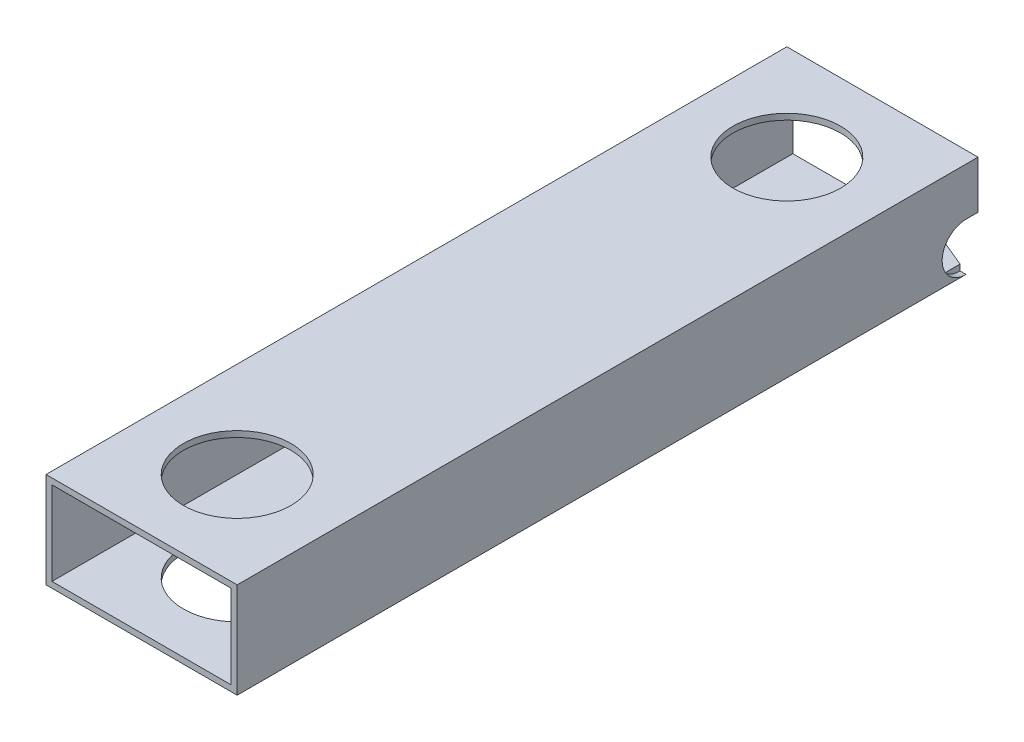
SolidWorks part; units mm, degrees
material "6061 Alloy"
ref_plane "Front Plane" through (0, 0, 0) normal (0, 0, 1) x (1, 0, 0)
ref_plane "Top Plane" through (0, 0, 0) normal (0, 1, 0) x (1, 0, 0)
ref_plane "Right Plane" through (0, 0, 0) normal (1, 0, 0) x (0, 0, -1)
sketch "Sketch1" plane through (0, 0, 0) normal (0, 0, 1) x (1, 0, 0)
  line L0 (-23.8125, 11.1125) -> (23.8125, 11.1125)
  line L2 (-25.4, 12.7) -> (25.4, 12.7)
  line L3 (-25.4, 12.7) -> (-25.4, -12.7)
  line L4 (-25.4, -12.7) -> (25.4, -12.7)
  line L5 (25.4, 12.7) -> (25.4, -12.7)
  line L10 (23.8125, 11.1125) -> (23.8125, -11.1125)
  line L11 (-23.8125, -11.1125) -> (23.8125, -11.1125)
  line L12 (-23.8125, 11.1125) -> (-23.8125, -11.1125)
  point P12 (0, 12.7)
  point P14 (25.4, 0)
  dimension "Wall Thickness" = 1.5875
  dimension "Outside Width" = 50.8
  dimension "Outside Height" = 25.4
  dimension "Inside Height" = 22.225
  dimension "Inside Width" = 47.625
sketch "Sketch2" plane through (0, 0, 0) normal (1, 0, 0) x (0, 0, -1)
  line L0 (98.425, 0) -> (-98.425, 0)
  point P4 (0, 0)
  point P7 (-98.425, 0)
  point P10 (98.425, 0)
  dimension "Length" = 196.85
sketch "Sketch3" plane through (0, 0, 0) normal (0, 0, 1) x (1, 0, 0)
  line L21 (25.4, 12.7) -> (-25.4, 12.7)
  line L22 (25.4, -12.7) -> (25.4, 12.7)
  line L23 (-25.4, -12.7) -> (25.4, -12.7)
  line L24 (-25.4, 12.7) -> (-25.4, -12.7)
  line L25 (25.4, 12.7) -> (-25.4, 12.7)
  line L26 (25.4, -12.7) -> (25.4, 12.7)
  line L27 (-25.4, -12.7) -> (25.4, -12.7)
  line L28 (-25.4, 12.7) -> (-25.4, -12.7)
  line L29 (23.8125, 11.1125) -> (-23.8125, 11.1125)
  line L30 (23.8125, -11.1125) -> (23.8125, 11.1125)
  line L31 (-23.8125, -11.1125) -> (23.8125, -11.1125)
  line L32 (-23.8125, 11.1125) -> (-23.8125, -11.1125)
  line L33 (23.8125, 11.1125) -> (-23.8125, 11.1125)
  line L34 (23.8125, -11.1125) -> (23.8125, 11.1125)
  line L35 (-23.8125, -11.1125) -> (23.8125, -11.1125)
  line L36 (-23.8125, 11.1125) -> (-23.8125, -11.1125)
  dimension "D1" = 0
  dimension "D2" = 0
extrude "Boss-Extrude1" add sketch "Sketch3" along normal up to vertex (98.425 mm away) and the other way up to vertex (98.425 mm away) up to point (0, 0, 98.425) other way up to point (0, 0, -98.425)
sketch "Drawing Reference" plane through (0, 0, 0) normal (1, 0, 0) x (0, 0, -1)
  line L0 (-98.425, 0) -> (98.425, 0) construction
  line L1 (0, -12.7) -> (0, 12.7) construction
  line L2 (-98.425, -12.7) -> (98.425, -12.7) construction
  line L5 (-98.425, 12.7) -> (98.425, 12.7) construction
  point P7 (-61.849, 0)
  point P8 (61.849, 0)
  dimension "D1" = 36.576
sketch "Sketch4" plane through (0, -12.7, 0) normal (0, -1, 0) x (1, 0, 0)
  line L0 (-25.4, 0) -> (0, 0) construction
  line L1 (-25.4, 98.425) -> (-25.4, -98.425) construction
  line L2 (0, 0) -> (0, -73.025) construction
  line L3 (0, 0) -> (0, 73.025) construction
  circle A0 centre (0, 73.025) radius 14.2875
  circle A1 centre (0, -73.025) radius 14.2875
extrude "Cut-Extrude3" cut sketch "Sketch4" against normal through all
sketch "Sketch5" plane through (25.4, 0, 0) normal (1, 0, 0) x (0, 0, -1)
  line L7 (98.425, -12.7) -> (98.425, 12.7) construction
  line L8 (98.425, 0) -> (98.425, -12.7)
  line L9 (98.425, -12.7) -> (95.25, -12.7)
  line L10 (95.25, 0) -> (98.425, 0)
  arc A0 (95.25, 0) -> (95.25, -12.7) centre (95.25, -6.35) ccw
  dimension "D1" = 6.35
extrude "Cut-Extrude5" cut sketch "Sketch5" against normal blind 1.5875
sketch "Sketch6" plane through (0, -12.7, 0) normal (0, -1, 0) x (1, 0, 0)
  line L0 (23.8125, -98.425) -> (23.8125, -95.25)
  line L1 (23.8125, -95.25) -> (16.1925, -98.425)
  line L2 (-25.4, -98.425) -> (23.8125, -98.425) construction
  line L3 (16.1925, -98.425) -> (23.8125, -98.425)
  dimension "D1" = 7.62
extrude "Cut-Extrude6" cut sketch "Sketch6" against normal blind 1.5875
equation "\"D1@Drawing Reference\"=\"Outside Width@Sketch1\" * 0.72"
